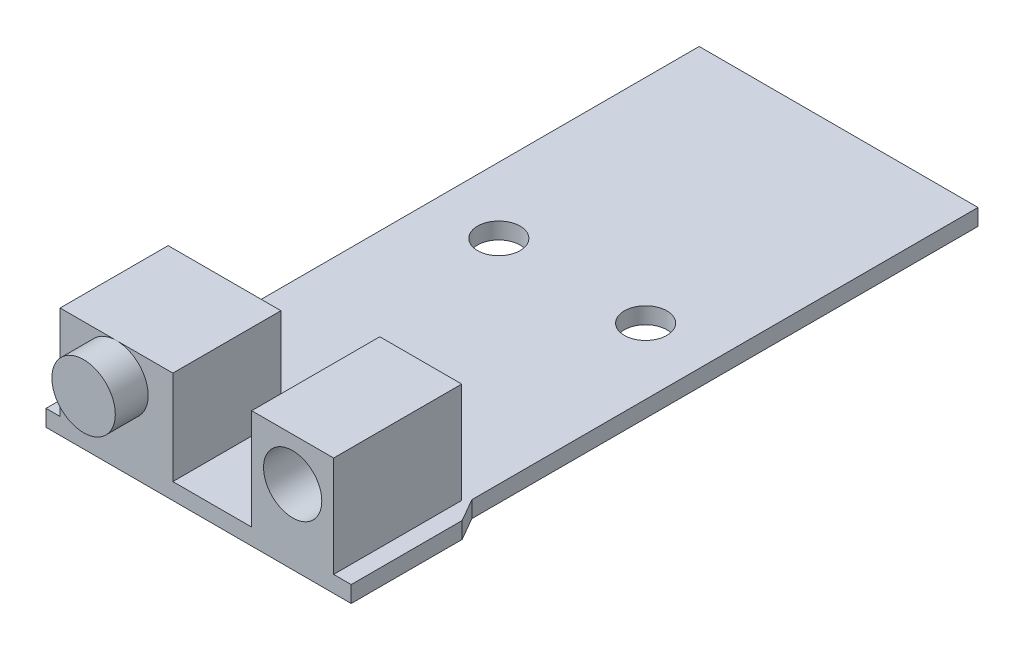
SolidWorks part; units mm, degrees
ref_plane "Front Plane" through (0, 0, 0) normal (0, 0, 1) x (1, 0, 0)
ref_plane "Top Plane" through (0, 0, 0) normal (0, 1, 0) x (1, 0, 0)
ref_plane "Right Plane" through (0, 0, 0) normal (1, 0, 0) x (0, 0, -1)
sketch "Sketch1" plane through (0, 0, 0) normal (0, 1, 0) x (1, 0, 0)
  line L0 (0, 0) -> (0, 69.2) construction
  line L1 (-15.075, 69.2) -> (15.075, 69.2)
  line L2 (15.075, 69.2) -> (15.075, 14.4682)
  line L3 (15.075, 14.4682) -> (16.5, 12)
  line L4 (16.5, 12) -> (16.5, 0)
  line L5 (16.5, 0) -> (-16.5, 0)
  line L6 (-16.5, 12) -> (-16.5, 0)
  line L7 (-15.075, 14.4682) -> (-16.5, 12)
  line L8 (-15.075, 69.2) -> (-15.075, 14.4682)
  dimension "D1" = 30.15
  dimension "D2" = 69.2
  dimension "D3" = 12
  dimension "D4" = 33
  dimension "D5" = 30
extrude "Boss-Extrude1" add sketch "Sketch1" along normal blind 1.778
sketch "Sketch2" plane through (0, 1.778, 0) normal (0, 1, 0) x (1, 0, 0)
  line L0 (-16.5, 0) -> (16.5, 0) construction
  line L1 (5.74, 13.85) -> (14.6, 13.85)
  line L2 (5.74, 13.85) -> (5.74, 0)
  line L3 (5.74, 0) -> (14.6, 0)
  line L4 (14.6, 13.85) -> (14.6, 0)
  line L5 (5.74, 13.85) -> (14.6, 0) construction
  line L6 (5.74, 0) -> (14.6, 13.85) construction
  line L7 (16.5, 0) -> (16.5, 12) construction
  point P4 (10.17, 6.925)
  dimension "D1" = 13.85
  dimension "D2" = 8.86
  dimension "D3" = 1.9
extrude "Boss-Extrude2" add sketch "Sketch2" along normal blind 10.9
sketch "Sketch3" plane through (0, 1.778, 0) normal (0, 1, 0) x (1, 0, 0)
  line L0 (-7.9375, 40.4) -> (7.9375, 40.4) construction
  line L1 (0, 40.4) -> (0, 0) construction
  line L2 (-16.5, 0) -> (5.74, 0) construction
  circle A0 centre (-7.9375, 40.4) radius 2.3
  circle A1 centre (7.9375, 40.4) radius 2.3
  dimension "D2" = 4.6
  dimension "D3" = 38.1
  dimension "D1" = 15.875
extrude "Cut-Extrude1" cut sketch "Sketch3" against normal through all
sketch "Sketch4" plane through (0, 1.778, 0) normal (0, 1, 0) x (1, 0, 0)
  line L0 (-16.5, 0) -> (5.74, 0) construction
  line L1 (-14.976, 0) -> (-2.784, 0)
  line L2 (-14.976, 0) -> (-14.976, 11.684)
  line L3 (-14.976, 11.684) -> (-2.784, 11.684)
  line L4 (-2.784, 0) -> (-2.784, 11.684)
  line L5 (-14.976, 0) -> (-2.784, 11.684) construction
  line L6 (-14.976, 11.684) -> (-2.784, 0) construction
  line L7 (-16.5, 12) -> (-16.5, 0) construction
  point P4 (-8.88, 5.842)
  dimension "D1" = 12.192
  dimension "D2" = 11.684
  dimension "D3" = 1.524
extrude "Boss-Extrude3" add sketch "Sketch4" along normal blind 10.16
sketch "Sketch5" plane through (0, 0, 0) normal (0, 0, 1) x (1, 0, 0)
  line L0 (-14.976, 11.938) -> (-2.784, 11.938) construction
  line L1 (-8.88, 8.509) -> (-8.88, 11.938) construction
  circle A0 centre (-8.88, 8.509) radius 3.429
  dimension "D1" = 6.858
extrude "Boss-Extrude4" add sketch "Sketch5" along normal blind 3.556
sketch "Sketch6" plane through (0, 0, 0) normal (0, 0, 1) x (1, 0, 0)
  line L0 (5.74, 12.678) -> (14.6, 12.678) construction
  line L1 (10.17, 12.678) -> (10.17, 8.0044) construction
  circle A0 centre (10.17, 8.0044) radius 3.1496
  dimension "D1" = 6.2992
  dimension "D2" = 1.524
extrude "Cut-Extrude2" cut sketch "Sketch6" against normal blind 11.656
